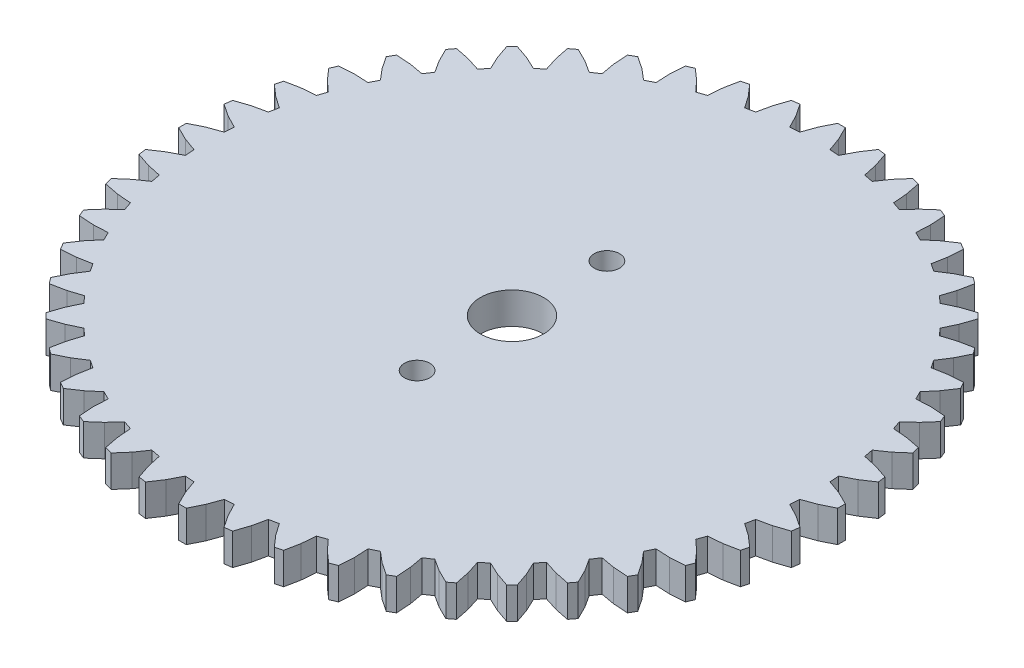
SolidWorks part; units mm, degrees
material "Acrylic (Medium-high impact)"
ref_plane "Front Plane" through (0, 0, 0) normal (0, 0, 1) x (1, 0, 0)
ref_plane "Top Plane" through (0, 0, 0) normal (0, 1, 0) x (1, 0, 0)
ref_plane "Right Plane" through (0, 0, 0) normal (1, 0, 0) x (0, 0, -1)
sketch "Sketch1" plane through (0, 0, 0) normal (0, 1, 0) x (1, 0, 0)
  line L0 (42.6708, 7.332) -> (44.3641, 6.7228)
  line L1 (44.3641, 6.7228) -> (46.0493, 5.8976)
  line L2 (46.0493, 5.8976) -> (46.0493, 4.9305)
  line L3 (46.0493, 4.9305) -> (44.3641, 4.1053)
  line L4 (44.3641, 4.1053) -> (42.6708, 3.4961)
  line L5 (42.6708, 3.4961) -> (42.5937, 2.3184)
  line L6 (42.5937, 2.3184) -> (44.1929, 1.4933)
  line L7 (44.1929, 1.4933) -> (45.7561, 0.4552)
  line L8 (45.7561, 0.4552) -> (45.6298, -0.5035)
  line L9 (45.6298, -0.5035) -> (43.8512, -1.1018)
  line L10 (43.8512, -1.1018) -> (42.093, -1.4848)
  line L11 (42.093, -1.4848) -> (41.8627, -2.6423)
  line L12 (41.8627, -2.6423) -> (43.3406, -3.669)
  line L13 (43.3406, -3.669) -> (44.7548, -4.9023)
  line L14 (44.7548, -4.9023) -> (44.5045, -5.8364)
  line L15 (44.5045, -5.8364) -> (42.663, -6.1973)
  line L16 (42.663, -6.1973) -> (40.8698, -6.3476)
  line L17 (40.8698, -6.3476) -> (40.4905, -7.4651)
  line L18 (40.4905, -7.4651) -> (41.8218, -8.676)
  line L19 (41.8218, -8.676) -> (43.0629, -10.0833)
  line L20 (43.0629, -10.0833) -> (42.6929, -10.9767)
  line L21 (42.6929, -10.9767) -> (40.82, -11.0943)
  line L22 (40.82, -11.0943) -> (39.0225, -11.0092)
  line L23 (39.0225, -11.0092) -> (38.5006, -12.0676)
  line L24 (38.5006, -12.0676) -> (39.6623, -13.4418)
  line L25 (39.6623, -13.4418) -> (40.7092, -14.9991)
  line L26 (40.7092, -14.9991) -> (40.2257, -15.8366)
  line L27 (40.2257, -15.8366) -> (38.3536, -15.7088)
  line L28 (38.3536, -15.7088) -> (36.5825, -15.3898)
  line L29 (36.5825, -15.3898) -> (35.9268, -16.371)
  line L30 (35.9268, -16.371) -> (36.8994, -17.8851)
  line L31 (36.8994, -17.8851) -> (37.734, -19.5657)
  line L32 (37.734, -19.5657) -> (37.1454, -20.3329)
  line L33 (37.1454, -20.3329) -> (35.3059, -19.9617)
  line L34 (35.3059, -19.9617) -> (33.5917, -19.4143)
  line L35 (33.5917, -19.4143) -> (32.8135, -20.3016)
  line L36 (32.8135, -20.3016) -> (33.58, -21.9296)
  line L37 (33.58, -21.9296) -> (34.1882, -23.7049)
  line L38 (34.1882, -23.7049) -> (33.5044, -24.3887)
  line L39 (33.5044, -24.3887) -> (31.7291, -23.7806)
  line L40 (31.7291, -23.7806) -> (30.1011, -23.014)
  line L41 (30.1011, -23.014) -> (29.2137, -23.7922)
  line L42 (29.2137, -23.7922) -> (29.7612, -25.5065)
  line L43 (29.7612, -25.5065) -> (30.1324, -27.3459)
  line L44 (30.1324, -27.3459) -> (29.3652, -27.9345)
  line L45 (29.3652, -27.9345) -> (27.6846, -27.0999)
  line L46 (27.6846, -27.0999) -> (26.1704, -26.1273)
  line L47 (26.1704, -26.1273) -> (25.1892, -26.783)
  line L48 (25.1892, -26.783) -> (25.5082, -28.5541)
  line L49 (25.5082, -28.5541) -> (25.6361, -30.4262)
  line L50 (25.6361, -30.4262) -> (24.7986, -30.9098)
  line L51 (24.7986, -30.9098) -> (23.2413, -29.8628)
  line L52 (23.2413, -29.8628) -> (21.8671, -28.7011)
  line L53 (21.8671, -28.7011) -> (20.8086, -29.223)
  line L54 (20.8086, -29.223) -> (20.8937, -31.0205)
  line L55 (20.8937, -31.0205) -> (20.7762, -32.8934)
  line L56 (20.7762, -32.8934) -> (19.8828, -33.2635)
  line L57 (19.8828, -33.2635) -> (18.4755, -32.0223)
  line L58 (18.4755, -32.0223) -> (17.2645, -30.691)
  line L59 (17.2645, -30.691) -> (16.147, -31.0704)
  line L60 (16.147, -31.0704) -> (15.9968, -32.8636)
  line L61 (15.9968, -32.8636) -> (15.6359, -34.7051)
  line L62 (15.6359, -34.7051) -> (14.7018, -34.9554)
  line L63 (14.7018, -34.9554) -> (13.4684, -33.5411)
  line L64 (13.4684, -33.5411) -> (12.4418, -32.0633)
  line L65 (12.4418, -32.0633) -> (11.2842, -32.2935)
  line L66 (11.2842, -32.2935) -> (10.9012, -34.0518)
  line L67 (10.9012, -34.0518) -> (10.303, -35.8303)
  line L68 (10.303, -35.8303) -> (9.3443, -35.9566)
  line L69 (9.3443, -35.9566) -> (8.3061, -34.3934)
  line L70 (8.3061, -34.3934) -> (7.4811, -32.7942)
  line L71 (7.4811, -32.7942) -> (6.3034, -32.8713)
  line L72 (6.3034, -32.8713) -> (5.6941, -34.5646)
  line L73 (5.6941, -34.5646) -> (4.869, -36.2498)
  line L74 (4.869, -36.2498) -> (3.9019, -36.2498)
  line L75 (3.9019, -36.2498) -> (3.0767, -34.5646)
  line L76 (3.0767, -34.5646) -> (2.4675, -32.8713)
  line L77 (2.4675, -32.8713) -> (1.2898, -32.7942)
  line L78 (1.2898, -32.7942) -> (0.4647, -34.3934)
  line L79 (0.4647, -34.3934) -> (-0.5735, -35.9566)
  line L80 (-0.5735, -35.9566) -> (-1.5322, -35.8303)
  line L81 (-1.5322, -35.8303) -> (-2.1304, -34.0518)
  line L82 (-2.1304, -34.0518) -> (-2.5134, -32.2935)
  line L83 (-2.5134, -32.2935) -> (-3.671, -32.0633)
  line L84 (-3.671, -32.0633) -> (-4.6976, -33.5411)
  line L85 (-4.6976, -33.5411) -> (-5.9309, -34.9554)
  line L86 (-5.9309, -34.9554) -> (-6.865, -34.7051)
  line L87 (-6.865, -34.7051) -> (-7.2259, -32.8636)
  line L88 (-7.2259, -32.8636) -> (-7.3762, -31.0704)
  line L89 (-7.3762, -31.0704) -> (-8.4937, -30.691)
  line L90 (-8.4937, -30.691) -> (-9.7047, -32.0223)
  line L91 (-9.7047, -32.0223) -> (-11.112, -33.2635)
  line L92 (-11.112, -33.2635) -> (-12.0054, -32.8934)
  line L93 (-12.0054, -32.8934) -> (-12.1229, -31.0205)
  line L94 (-12.1229, -31.0205) -> (-12.0378, -29.223)
  line L95 (-12.0378, -29.223) -> (-13.0963, -28.7011)
  line L96 (-13.0963, -28.7011) -> (-14.4705, -29.8628)
  line L97 (-14.4705, -29.8628) -> (-16.0278, -30.9098)
  line L98 (-16.0278, -30.9098) -> (-16.8653, -30.4262)
  line L99 (-16.8653, -30.4262) -> (-16.7374, -28.5541)
  line L100 (-16.7374, -28.5541) -> (-16.4184, -26.783)
  line L101 (-16.4184, -26.783) -> (-17.3996, -26.1273)
  line L102 (-17.3996, -26.1273) -> (-18.9137, -27.0999)
  line L103 (-18.9137, -27.0999) -> (-20.5944, -27.9345)
  line L104 (-20.5944, -27.9345) -> (-21.3616, -27.3459)
  line L105 (-21.3616, -27.3459) -> (-20.9903, -25.5065)
  line L106 (-20.9903, -25.5065) -> (-20.4429, -23.7922)
  line L107 (-20.4429, -23.7922) -> (-21.3303, -23.014)
  line L108 (-21.3303, -23.014) -> (-22.9583, -23.7806)
  line L109 (-22.9583, -23.7806) -> (-24.7335, -24.3887)
  line L110 (-24.7335, -24.3887) -> (-25.4174, -23.7049)
  line L111 (-25.4174, -23.7049) -> (-24.8092, -21.9296)
  line L112 (-24.8092, -21.9296) -> (-24.0427, -20.3016)
  line L113 (-24.0427, -20.3016) -> (-24.8209, -19.4143)
  line L114 (-24.8209, -19.4143) -> (-26.5351, -19.9617)
  line L115 (-26.5351, -19.9617) -> (-28.3745, -20.3329)
  line L116 (-28.3745, -20.3329) -> (-28.9632, -19.5657)
  line L117 (-28.9632, -19.5657) -> (-28.1286, -17.8851)
  line L118 (-28.1286, -17.8851) -> (-27.156, -16.371)
  line L119 (-27.156, -16.371) -> (-27.8117, -15.3898)
  line L120 (-27.8117, -15.3898) -> (-29.5827, -15.7088)
  line L121 (-29.5827, -15.7088) -> (-31.4549, -15.8366)
  line L122 (-31.4549, -15.8366) -> (-31.9384, -14.9991)
  line L123 (-31.9384, -14.9991) -> (-30.8915, -13.4418)
  line L124 (-30.8915, -13.4418) -> (-29.7297, -12.0676)
  line L125 (-29.7297, -12.0676) -> (-30.2516, -11.0092)
  line L126 (-30.2516, -11.0092) -> (-32.0492, -11.0943)
  line L127 (-32.0492, -11.0943) -> (-33.9221, -10.9767)
  line L128 (-33.9221, -10.9767) -> (-34.2921, -10.0833)
  line L129 (-34.2921, -10.0833) -> (-33.0509, -8.676)
  line L130 (-33.0509, -8.676) -> (-31.7197, -7.4651)
  line L131 (-31.7197, -7.4651) -> (-32.099, -6.3476)
  line L132 (-32.099, -6.3476) -> (-33.8922, -6.1973)
  line L133 (-33.8922, -6.1973) -> (-35.7337, -5.8364)
  line L134 (-35.7337, -5.8364) -> (-35.984, -4.9023)
  line L135 (-35.984, -4.9023) -> (-34.5698, -3.669)
  line L136 (-34.5698, -3.669) -> (-33.0919, -2.6423)
  line L137 (-33.0919, -2.6423) -> (-33.3222, -1.4848)
  line L138 (-33.3222, -1.4848) -> (-35.0804, -1.1018)
  line L139 (-35.0804, -1.1018) -> (-36.8589, -0.5035)
  line L140 (-36.8589, -0.5035) -> (-36.9853, 0.4552)
  line L141 (-36.9853, 0.4552) -> (-35.4221, 1.4933)
  line L142 (-35.4221, 1.4933) -> (-33.8228, 2.3184)
  line L143 (-33.8228, 2.3184) -> (-33.8999, 3.4961)
  line L144 (-33.8999, 3.4961) -> (-35.5933, 4.1053)
  line L145 (-35.5933, 4.1053) -> (-37.2785, 4.9305)
  line L146 (-37.2785, 4.9305) -> (-37.2785, 5.8976)
  line L147 (-37.2785, 5.8976) -> (-35.5933, 6.7228)
  line L148 (-35.5933, 6.7228) -> (-33.8999, 7.332)
  line L149 (-33.8999, 7.332) -> (-33.8228, 8.5097)
  line L150 (-33.8228, 8.5097) -> (-35.4221, 9.3348)
  line L151 (-35.4221, 9.3348) -> (-36.9853, 10.3729)
  line L152 (-36.9853, 10.3729) -> (-36.8589, 11.3316)
  line L153 (-36.8589, 11.3316) -> (-35.0804, 11.9299)
  line L154 (-35.0804, 11.9299) -> (-33.3222, 12.3129)
  line L155 (-33.3222, 12.3129) -> (-33.0919, 13.4704)
  line L156 (-33.0919, 13.4704) -> (-34.5698, 14.4971)
  line L157 (-34.5698, 14.4971) -> (-35.984, 15.7304)
  line L158 (-35.984, 15.7304) -> (-35.7337, 16.6645)
  line L159 (-35.7337, 16.6645) -> (-33.8922, 17.0254)
  line L160 (-33.8922, 17.0254) -> (-32.099, 17.1757)
  line L161 (-32.099, 17.1757) -> (-31.7197, 18.2932)
  line L162 (-31.7197, 18.2932) -> (-33.0509, 19.5041)
  line L163 (-33.0509, 19.5041) -> (-34.2921, 20.9114)
  line L164 (-34.2921, 20.9114) -> (-33.9221, 21.8048)
  line L165 (-33.9221, 21.8048) -> (-32.0492, 21.9224)
  line L166 (-32.0492, 21.9224) -> (-30.2516, 21.8373)
  line L167 (-30.2516, 21.8373) -> (-29.7297, 22.8957)
  line L168 (-29.7297, 22.8957) -> (-30.8915, 24.2699)
  line L169 (-30.8915, 24.2699) -> (-31.9384, 25.8272)
  line L170 (-31.9384, 25.8272) -> (-31.4549, 26.6647)
  line L171 (-31.4549, 26.6647) -> (-29.5827, 26.5368)
  line L172 (-29.5827, 26.5368) -> (-27.8117, 26.2178)
  line L173 (-27.8117, 26.2178) -> (-27.156, 27.1991)
  line L174 (-27.156, 27.1991) -> (-28.1286, 28.7132)
  line L175 (-28.1286, 28.7132) -> (-28.9632, 30.3938)
  line L176 (-28.9632, 30.3938) -> (-28.3745, 31.161)
  line L177 (-28.3745, 31.161) -> (-26.5351, 30.7898)
  line L178 (-26.5351, 30.7898) -> (-24.8209, 30.2424)
  line L179 (-24.8209, 30.2424) -> (-24.0427, 31.1297)
  line L180 (-24.0427, 31.1297) -> (-24.8092, 32.7577)
  line L181 (-24.8092, 32.7577) -> (-25.4174, 34.533)
  line L182 (-25.4174, 34.533) -> (-24.7335, 35.2168)
  line L183 (-24.7335, 35.2168) -> (-22.9583, 34.6087)
  line L184 (-22.9583, 34.6087) -> (-21.3303, 33.8421)
  line L185 (-21.3303, 33.8421) -> (-20.4429, 34.6203)
  line L186 (-20.4429, 34.6203) -> (-20.9903, 36.3346)
  line L187 (-20.9903, 36.3346) -> (-21.3616, 38.174)
  line L188 (-21.3616, 38.174) -> (-20.5944, 38.7626)
  line L189 (-20.5944, 38.7626) -> (-18.9137, 37.928)
  line L190 (-18.9137, 37.928) -> (-17.3996, 36.9554)
  line L191 (-17.3996, 36.9554) -> (-16.4184, 37.6111)
  line L192 (-16.4184, 37.6111) -> (-16.7374, 39.3822)
  line L193 (-16.7374, 39.3822) -> (-16.8653, 41.2543)
  line L194 (-16.8653, 41.2543) -> (-16.0278, 41.7379)
  line L195 (-16.0278, 41.7379) -> (-14.4705, 40.6909)
  line L196 (-14.4705, 40.6909) -> (-13.0963, 39.5292)
  line L197 (-13.0963, 39.5292) -> (-12.0378, 40.0511)
  line L198 (-12.0378, 40.0511) -> (-12.1229, 41.8486)
  line L199 (-12.1229, 41.8486) -> (-12.0054, 43.7215)
  line L200 (-12.0054, 43.7215) -> (-11.112, 44.0916)
  line L201 (-11.112, 44.0916) -> (-9.7047, 42.8504)
  line L202 (-9.7047, 42.8504) -> (-8.4937, 41.5191)
  line L203 (-8.4937, 41.5191) -> (-7.3762, 41.8985)
  line L204 (-7.3762, 41.8985) -> (-7.2259, 43.6917)
  line L205 (-7.2259, 43.6917) -> (-6.865, 45.5332)
  line L206 (-6.865, 45.5332) -> (-5.9309, 45.7835)
  line L207 (-5.9309, 45.7835) -> (-4.6976, 44.3692)
  line L208 (-4.6976, 44.3692) -> (-3.671, 42.8914)
  line L209 (-3.671, 42.8914) -> (-2.5134, 43.1216)
  line L210 (-2.5134, 43.1216) -> (-2.1304, 44.8799)
  line L211 (-2.1304, 44.8799) -> (-1.5322, 46.6584)
  line L212 (-1.5322, 46.6584) -> (-0.5735, 46.7847)
  line L213 (-0.5735, 46.7847) -> (0.4647, 45.2215)
  line L214 (0.4647, 45.2215) -> (1.2898, 43.6223)
  line L215 (1.2898, 43.6223) -> (2.4675, 43.6994)
  line L216 (2.4675, 43.6994) -> (3.0767, 45.3927)
  line L217 (3.0767, 45.3927) -> (3.9019, 47.0779)
  line L218 (3.9019, 47.0779) -> (4.869, 47.0779)
  line L219 (4.869, 47.0779) -> (5.6941, 45.3927)
  line L220 (5.6941, 45.3927) -> (6.3034, 43.6994)
  line L221 (6.3034, 43.6994) -> (7.4811, 43.6223)
  line L222 (7.4811, 43.6223) -> (8.3061, 45.2215)
  line L223 (8.3061, 45.2215) -> (9.3443, 46.7847)
  line L224 (9.3443, 46.7847) -> (10.303, 46.6584)
  line L225 (10.303, 46.6584) -> (10.9012, 44.8799)
  line L226 (10.9012, 44.8799) -> (11.2842, 43.1216)
  line L227 (11.2842, 43.1216) -> (12.4418, 42.8914)
  line L228 (12.4418, 42.8914) -> (13.4684, 44.3692)
  line L229 (13.4684, 44.3692) -> (14.7018, 45.7835)
  line L230 (14.7018, 45.7835) -> (15.6359, 45.5332)
  line L231 (15.6359, 45.5332) -> (15.9968, 43.6917)
  line L232 (15.9968, 43.6917) -> (16.147, 41.8985)
  line L233 (16.147, 41.8985) -> (17.2645, 41.5191)
  line L234 (17.2645, 41.5191) -> (18.4755, 42.8504)
  line L235 (18.4755, 42.8504) -> (19.8828, 44.0916)
  line L236 (19.8828, 44.0916) -> (20.7762, 43.7215)
  line L237 (20.7762, 43.7215) -> (20.8937, 41.8486)
  line L238 (20.8937, 41.8486) -> (20.8086, 40.0511)
  line L239 (20.8086, 40.0511) -> (21.8671, 39.5292)
  line L240 (21.8671, 39.5292) -> (23.2413, 40.6909)
  line L241 (23.2413, 40.6909) -> (24.7986, 41.7379)
  line L242 (24.7986, 41.7379) -> (25.6361, 41.2543)
  line L243 (25.6361, 41.2543) -> (25.5082, 39.3822)
  line L244 (25.5082, 39.3822) -> (25.1892, 37.6111)
  line L245 (25.1892, 37.6111) -> (26.1704, 36.9554)
  line L246 (26.1704, 36.9554) -> (27.6846, 37.928)
  line L247 (27.6846, 37.928) -> (29.3652, 38.7626)
  line L248 (29.3652, 38.7626) -> (30.1324, 38.174)
  line L249 (30.1324, 38.174) -> (29.7612, 36.3346)
  line L250 (29.7612, 36.3346) -> (29.2137, 34.6203)
  line L251 (29.2137, 34.6203) -> (30.1011, 33.8421)
  line L252 (30.1011, 33.8421) -> (31.7291, 34.6087)
  line L253 (31.7291, 34.6087) -> (33.5044, 35.2168)
  line L254 (33.5044, 35.2168) -> (34.1882, 34.533)
  line L255 (34.1882, 34.533) -> (33.58, 32.7577)
  line L256 (33.58, 32.7577) -> (32.8135, 31.1297)
  line L257 (32.8135, 31.1297) -> (33.5917, 30.2424)
  line L258 (33.5917, 30.2424) -> (35.3059, 30.7898)
  line L259 (35.3059, 30.7898) -> (37.1454, 31.161)
  line L260 (37.1454, 31.161) -> (37.734, 30.3938)
  line L261 (37.734, 30.3938) -> (36.8994, 28.7132)
  line L262 (36.8994, 28.7132) -> (35.9268, 27.1991)
  line L263 (35.9268, 27.1991) -> (36.5825, 26.2178)
  line L264 (36.5825, 26.2178) -> (38.3536, 26.5368)
  line L265 (38.3536, 26.5368) -> (40.2257, 26.6647)
  line L266 (40.2257, 26.6647) -> (40.7092, 25.8272)
  line L267 (40.7092, 25.8272) -> (39.6623, 24.2699)
  line L268 (39.6623, 24.2699) -> (38.5006, 22.8957)
  line L269 (38.5006, 22.8957) -> (39.0225, 21.8373)
  line L270 (39.0225, 21.8373) -> (40.82, 21.9224)
  line L271 (40.82, 21.9224) -> (42.6929, 21.8048)
  line L272 (42.6929, 21.8048) -> (43.0629, 20.9114)
  line L273 (43.0629, 20.9114) -> (41.8218, 19.5041)
  line L274 (41.8218, 19.5041) -> (40.4905, 18.2932)
  line L275 (40.4905, 18.2932) -> (40.8698, 17.1757)
  line L276 (40.8698, 17.1757) -> (42.663, 17.0254)
  line L277 (42.663, 17.0254) -> (44.5045, 16.6645)
  line L278 (44.5045, 16.6645) -> (44.7548, 15.7304)
  line L279 (44.7548, 15.7304) -> (43.3406, 14.4971)
  line L280 (43.3406, 14.4971) -> (41.8627, 13.4704)
  line L281 (41.8627, 13.4704) -> (42.093, 12.3129)
  line L282 (42.093, 12.3129) -> (43.8512, 11.9299)
  line L283 (43.8512, 11.9299) -> (45.6298, 11.3316)
  line L284 (45.6298, 11.3316) -> (45.7561, 10.3729)
  line L285 (45.7561, 10.3729) -> (44.1929, 9.3348)
  line L286 (44.1929, 9.3348) -> (42.5937, 8.5097)
  line L287 (42.5937, 8.5097) -> (42.6708, 7.332)
  line L288 (4.3854, 47.0779) -> (4.3854, -36.2498) construction
  line L289 (-37.2785, 5.414) -> (46.0493, 5.414) construction
  point P292 (4.3854, 5.414)
sketch "Sketch3" plane through (0, 0, 0) normal (0, 1, 0) x (1, 0, 0)
  line L0 (-37.2785, 5.414) -> (46.0493, 5.414) construction
  circle A0 centre (4.3854, 5.414) radius 4
  dimension "D1" = 8
sketch "Sketch4" plane through (0, 0, 0) normal (0, 1, 0) x (1, 0, 0)
  line L0 (-12.0218, 5.414) -> (22.4064, 5.414) construction
  line L1 (-37.2785, 5.414) -> (46.0493, 5.414) construction
  line L2 (4.3854, 47.0779) -> (4.3854, -36.2498) construction
  circle A0 centre (4.3854, 17.414) radius 1.6
  circle A1 centre (4.3854, -6.586) radius 1.6
  dimension "D1" = 3.2
  dimension "D2" = 12
extrude "Boss-Extrude2" add sketch "Sketch1" along normal blind 4
extrude "Cut-Extrude1" cut sketch "Sketch3" along normal up to next
extrude "Cut-Extrude2" cut sketch "Sketch4" along normal up to next
